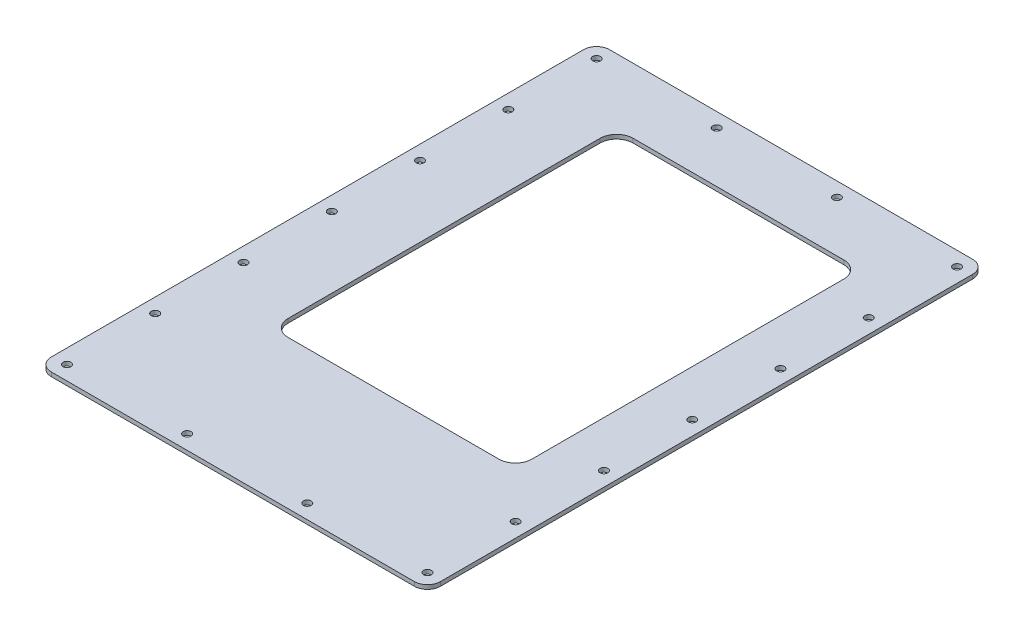
SolidWorks part; units mm, degrees
material "5052-H32"
ref_plane "Front Plane" through (0, 0, 0) normal (0, 0, 1) x (1, 0, 0)
ref_plane "Top Plane" through (0, 0, 0) normal (0, 1, 0) x (1, 0, 0)
ref_plane "Right Plane" through (0, 0, 0) normal (1, 0, 0) x (0, 0, -1)
sketch "Sketch9" plane through (0, 0, 0) normal (0, 1, 0) x (1, 0, 0)
  line L0 (-149.5, 0) -> (-149.5, 429)
  line L13 (-149.5, 429) -> (149.5, 429)
  line L14 (103.1625, 113.9438) -> (-84.1625, 113.9438)
  line L19 (149.5, 429) -> (149.5, 0)
  line L20 (103.1625, 113.9438) -> (103.1625, 379.0563)
  line L21 (103.1625, 379.0563) -> (-84.1625, 379.0563)
  line L22 (-84.1625, 113.9438) -> (-84.1625, 379.0563)
  line L23 (103.1625, 246.5) -> (-84.1625, 246.5) construction
  line L24 (9.5, 379.0562) -> (9.5, 113.9438) construction
  line L25 (-149.5, 0) -> (149.5, 0)
  point P8 (0, 0)
  point P19 (0, 0)
  dimension "D3" = 265.1125
  dimension "D4" = 187.325
  dimension "D1" = 299
  dimension "D2" = 429
  dimension "D6" = 140
  dimension "D5" = 182.5
extrude "Boss-Extrude7" add sketch "Sketch9" along normal blind 3.175 separate body contours L0 L25 L19 L13 L14 L22 L21 L20 region at (-144.2708, 0, -214.5)
fillet "Fillet4" radius 10 4 edges at (-149.5, 1.5875, -429) (149.5, 1.5875, -429) (-149.5, 1.5875, 0) (149.5, 1.5875, 0)
fillet "Fillet5" radius 12.7 4 edges at (-84.1625, 1.5875, -113.9438) (103.1625, 1.5875, -113.9438) (103.1625, 1.5875, -379.0563) (-84.1625, 1.5875, -379.0563)
sketch "Sketch10" plane through (0, 3.175, 0) normal (0, 1, 0) x (1, 0, 0)
  line L0 (-149.5, 10) -> (-149.5, 419) construction
  line L1 (-139.5, 0) -> (139.5, 0) construction
  circle A0 centre (-138.5, 11) radius 3
  circle A1 centre (-46.1667, 11) radius 3
  circle A2 centre (46.1667, 11) radius 3
  circle A3 centre (138.5, 11) radius 3
  circle A56 centre (-138.5, 78.8333) radius 3
  circle A57 centre (-138.5, 146.6667) radius 3
  circle A58 centre (-138.5, 214.5) radius 3
  circle A59 centre (-138.5, 282.3333) radius 3
  circle A60 centre (-138.5, 350.1667) radius 3
  circle A61 centre (-138.5, 418) radius 3
  circle A68 centre (138.5, 78.8333) radius 3
  circle A72 centre (138.5, 146.6667) radius 3
  circle A76 centre (138.5, 214.5) radius 3
  circle A80 centre (138.5, 282.3333) radius 3
  circle A84 centre (138.5, 350.1667) radius 3
  circle A86 centre (-46.1667, 418) radius 3
  circle A87 centre (46.1667, 418) radius 3
  circle A88 centre (138.5, 418) radius 3
  circle A102 centre (-46.1667, 78.8333) radius 3 [skipped]
  circle A103 centre (46.1667, 78.8333) radius 3 [skipped]
  circle A104 centre (-46.1667, 146.6667) radius 3 [skipped]
  circle A105 centre (46.1667, 146.6667) radius 3 [skipped]
  circle A106 centre (-46.1667, 214.5) radius 3 [skipped]
  circle A107 centre (46.1667, 214.5) radius 3 [skipped]
  circle A108 centre (-46.1667, 282.3333) radius 3 [skipped]
  circle A109 centre (46.1667, 282.3333) radius 3 [skipped]
  circle A110 centre (-46.1667, 350.1667) radius 3 [skipped]
  circle A111 centre (46.1667, 350.1667) radius 3 [skipped]
  dimension "D1" = 6
  dimension "D2" = 11
  dimension "D3" = 11
  dimension "D6" = 67.8333
  dimension "D7" = 92.3333
  dimension "D4" = 4
extrude "Cut-Extrude1" cut sketch "Sketch10" against normal up to surface (3.175 mm away) up to face at (9.5, 0, -246.5)
equation "\"W\"= 255"
equation "\"L\"= 385"
equation "\"Offset\"= 30"
equation "\"H\"= 110"
equation "\"Compartment Width\"= 80"
equation "\"T\"= 4.7625 * 2 / 3"
equation "\"Inside Fillet Radius\"= 5.55625"
equation "\"Hole\"=15"
equation "\"Wheel to Wall\"= 50"
equation "\"D1@Sketch9\"=\"W\"+44"
equation "\"D2@Sketch9\"=\"L\"+44"
equation "\"D6@Sketch10\"=(\"L\"+22)/6"
equation "\"D7@Sketch10\"=(\"W\"+22)/3"
equation "\"D5@Sketch9\"=(\"L\"/2+20)-\"Offset\""
